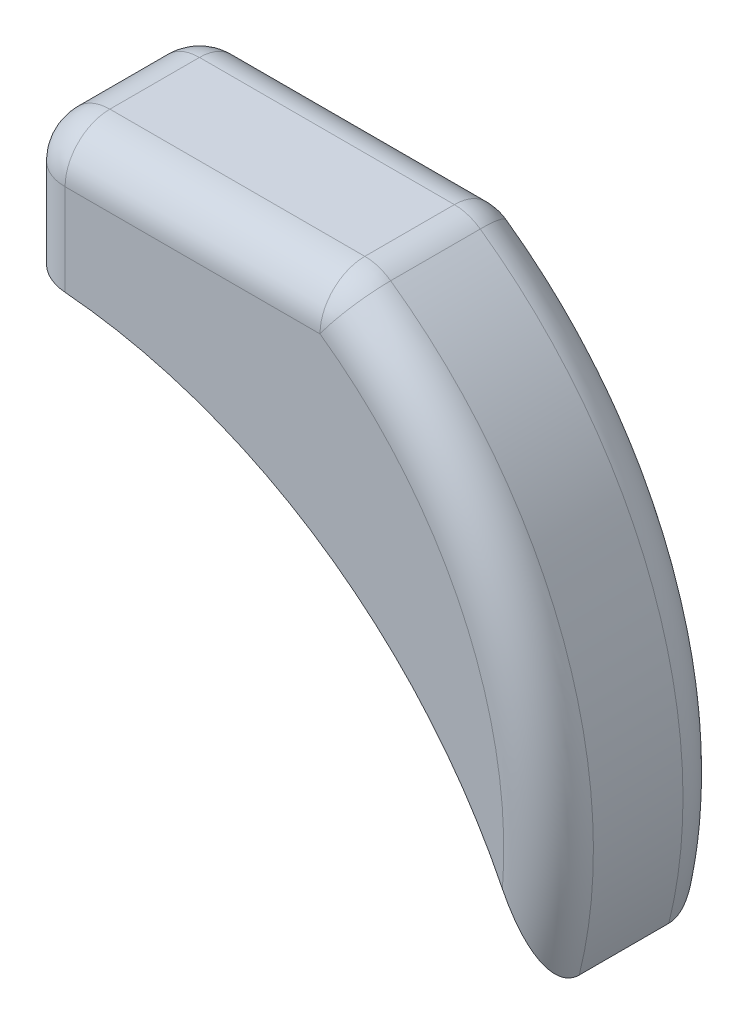
SolidWorks part; units mm, degrees
ref_plane "Plan de face" through (0, 0, 0) normal (0, 0, 1) x (1, 0, 0)
ref_plane "Plan de dessus" through (0, 0, 0) normal (0, 1, 0) x (1, 0, 0)
ref_plane "Plan de droite" through (0, 0, 0) normal (1, 0, 0) x (0, 0, -1)
sketch "Esquisse1" plane through (0, 0, 0) normal (0, 0, 1) x (1, 0, 0)
  line L0 (-47.6925, 0) -> (47.6925, 0) construction
  line L1 (-35, 15) -> (35, 15)
  line L2 (-35, 15) -> (-35, -15)
  line L3 (-35, -15) -> (35, -15)
  line L4 (35, 15) -> (35, -15)
  line L5 (0, 50.3454) -> (0, -36.0614) construction
  line L6 (-35, -15) -> (-35, -275.1686)
  line L7 (-35, -135) -> (85, -135) construction
  circle A0 centre (-35, -135) radius 120
  arc A1 (35, 15) -> (79.7824, -100) centre (-24.0656, -74.2203) cw
  dimension "D1" = 240
  dimension "D4" = 35
  dimension "D5" = 107
  dimension "D2" = 30
  dimension "D3" = 70
extrude "Boss.-Extru.1" add sketch "Esquisse1" along normal mid plane 40 contours A1 L4 L3 A0 | L4 L1 L2 L3 region at (0, 0, 0) region at (51.6227, -34.078, 0)
sketch "Esquisse2" plane through (-35, 0, 0) normal (-1, 0, 0) x (0, 0, 1)
  line L0 (0, 15) -> (0, -15) construction
  line L2 (20, -15) -> (-20, -15) construction
  line L3 (20, 0) -> (-20, 0) construction
  line L6 (20, 15) -> (-20, 15) construction
  line L7 (20, 15) -> (20, -15) construction
  circle A0 centre (0, 0) radius 13.505
  dimension "D1" = 27.01
sketch "Esquisse5" plane through (0, 0, 0) normal (0, 0, 1) x (1, 0, 0)
  line L0 (-18.0517, 0) -> (47.2247, 0) construction
  line L1 (15, -9.0766) -> (15, -9)
  line L2 (15, -9.0766) -> (15, -39)
  line L3 (15, -39) -> (37, -39)
  line L4 (37, -9) -> (15, -9)
  line L5 (-35, 15) -> (-35, -15) construction
  line L6 (37, -9) -> (37, -39)
  line L8 (37, -9) -> (37, 20.4551) construction
  line L9 (26, -39) -> (26, -9) construction
  arc A0 (79.7824, -100) -> (-35, -15) centre (-35, -135) ccw construction
  arc A1 (79.7824, -100) -> (-35, -15) centre (-35, -135) ccw construction
  dimension "D1" = 30
  dimension "D2" = 22
  dimension "D4" = 50
sketch "Esquisse6" plane through (-35, 0, 0) normal (-1, 0, 0) x (0, 0, 1)
  line L0 (20, 15) -> (-20, 15) construction
  line L1 (-20, 15) -> (20, 15)
  line L2 (-20, 15) -> (-20, -25)
  line L3 (-20, -25) -> (20, -25)
  line L4 (20, 15) -> (20, -25)
  line L6 (20, 15) -> (20, -15) construction
  line L7 (-20, 15) -> (-20, -15) construction
  line L8 (20, -15) -> (-20, -15) construction
  dimension "D1" = 10
sketch "Esquisse7" [suppressed] plane through (-30, 0, 0) normal (-1, 0, 0) x (0, 0, 1)
  line L0 (-50.7126, 0) -> (32.9762, 0) construction
  line L1 (0, 30.6791) -> (0, -28.4968) construction
  circle A0 centre (-15, 15) radius 1.5
  circle A1 centre (-15, -15) radius 1.5
  circle A2 centre (15, -15) radius 1.5
  circle A3 centre (15, 15) radius 1.5
  dimension "D1" = 3
  dimension "D2" = 30
  dimension "D3" = 30
fillet "Congé7" radius 10 8 edges at (75.6413, -35.3932, 20) (35, 15, 0) (0, 15, -20) (0, 15, 20) (-35, 15, 0) (-35, 0, -20) (-35, 0, 20) (75.6413, -35.3932, -20)
sketch "Esquisse13" plane through (26.2713, -32.6178, 0) normal (-0.5112, -0.8594, 0) x (-0.8594, 0.5112, 0)
  circle A0 centre (33.1157, 0) radius 1.5
  circle A1 centre (-42.4822, 0) radius 1.5
  dimension "D1" = 3
extrude "Enlèv. mat.-Extru.1" cut sketch "Esquisse13" along normal blind 15
extrude "Enlèv. mat.-Extru.2" cut sketch "Esquisse13<2>" against normal blind 5
sketch "Esquisse13<2>" plane through (26.2713, -32.6178, 0) normal (-0.5112, -0.8594, 0) x (-0.8594, 0.5112, 0) same geometry as "Esquisse13"
ref_plane "Plan1" through (-7.4651, -12.5494, 0) normal (-0.5112, -0.8594, 0) x (-0.8594, 0.5112, 0)
ref_plane "Plan2" through (-17.69, -29.7382, 0) normal (-0.5112, -0.8594, 0) x (-0.8594, 0.5112, 0)
sketch "Esquisse16" plane through (-17.69, -29.7382, 0) normal (-0.5112, -0.8594, 0) x (-0.8594, 0.5112, 0)
  circle A0 centre (-6.1385, 0) radius 1.5
  circle A1 centre (-81.7364, 0) radius 1.5
  circle A2 centre (-81.7364, 0) radius 1.5 construction
  dimension "D1" = 3
